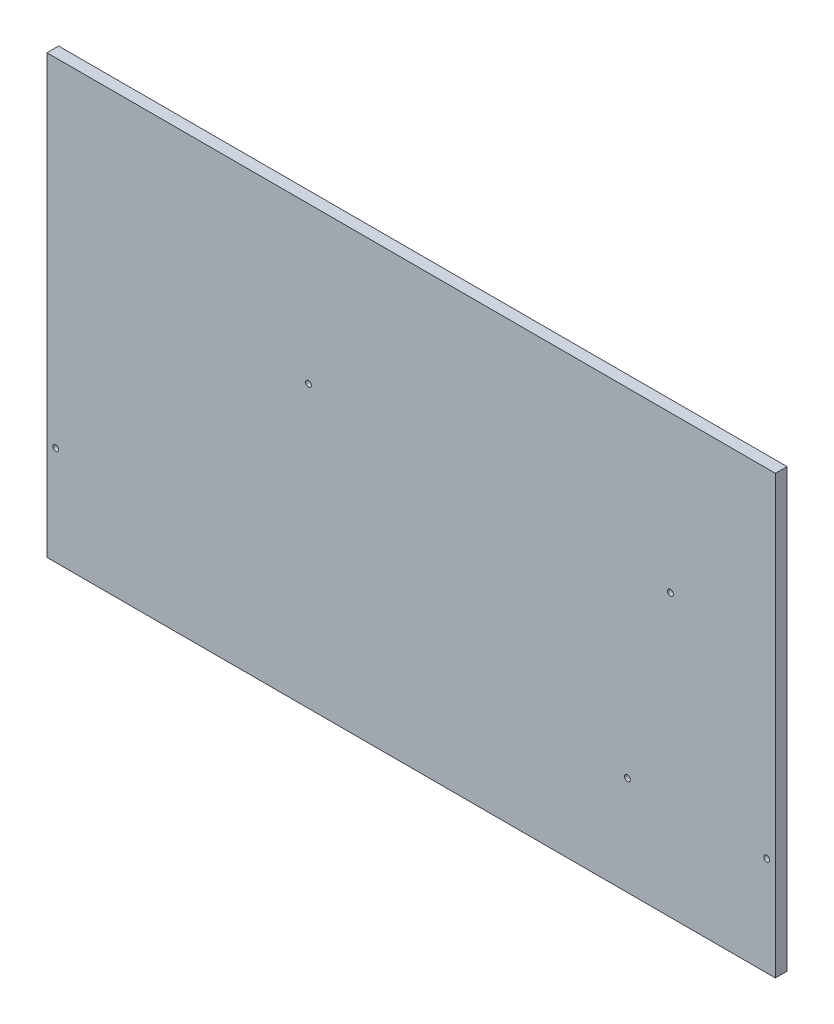
SolidWorks part; units mm, degrees
ref_plane "Alzado" through (0, 0, 0) normal (0, 0, 1) x (1, 0, 0)
ref_plane "Planta" through (0, 0, 0) normal (0, 1, 0) x (1, 0, 0)
ref_plane "Vista lateral" through (0, 0, 0) normal (1, 0, 0) x (0, 0, -1)
sketch "Sketch1" plane through (0, 0, 0) normal (0, 0, 1) x (1, 0, 0)
  line L1 (-99.7768, 38.058) -> (100.2232, 38.058)
  line L2 (-99.7768, 38.058) -> (-99.7768, -111.942)
  line L3 (-99.7768, -111.942) -> (100.2232, -111.942)
  line L4 (100.2232, 38.058) -> (100.2232, -111.942)
  dimension "D1" = 200
  dimension "D2" = 150
extrude "Boss-Extrude1" add sketch "Sketch1" along normal blind 4
sketch "Sketch2" plane through (100.2232, 0, 0) normal (1, 0, 0) x (0, 0, -1)
  line L1 (-4, 38.058) -> (0, 38.058)
  line L2 (-4, 38.058) -> (-4, -111.942)
  line L3 (-4, -111.942) -> (0, -111.942)
  line L4 (0, 38.058) -> (0, -111.942)
extrude "Boss-Extrude2" add sketch "Sketch2" along normal blind 50
sketch "Sketch3" plane through (0, 0, 0) normal (0, 0, -1) x (-1, 0, 0)
  line L0 (99.7768, 38.058) -> (99.7768, -111.942) construction
  line L1 (99.7768, -111.942) -> (-150.2232, -111.942) construction
  circle A0 centre (96.7768, -77.942) radius 1
  dimension "D1" = 3
  dimension "D2" = 34
extrude "Cut-Extrude1" cut sketch "Sketch3" against normal blind 21
sketch "Sketch4" plane through (0, 0, 0) normal (0, 0, -1) x (-1, 0, 0)
  line L0 (-150.2232, -111.942) -> (-150.2232, 38.058) construction
  circle A0 centre (-147.2232, -77.942) radius 1
  dimension "D1" = 3
extrude "Cut-Extrude2" cut sketch "Sketch4" against normal blind 21
sketch "Sketch5" plane through (0, 0, 0) normal (0, 0, -1) x (-1, 0, 0)
  circle A0 centre (-99.4232, -77.942) radius 1
  circle A1 centre (-147.2232, -77.942) radius 1 construction
  dimension "D1" = 47.8
extrude "Cut-Extrude3" cut sketch "Sketch5" against normal blind 21
sketch "Sketch6" plane through (0, 0, 4) normal (0, 0, 1) x (1, 0, 0)
  line L0 (150.2232, -111.942) -> (150.2232, -15.442) construction
  line L1 (150.2232, 38.058) -> (150.2232, -111.942) construction
  line L2 (150.2232, -15.442) -> (114.2032, -15.442) construction
  circle A0 centre (114.2032, -15.442) radius 1
  circle A1 centre (-10.0268, -15.442) radius 1
  dimension "D3" = 124.23
  dimension "D1" = 96.5
  dimension "D2" = 36.02
extrude "Cut-Extrude4" cut sketch "Sketch6" against normal through all
